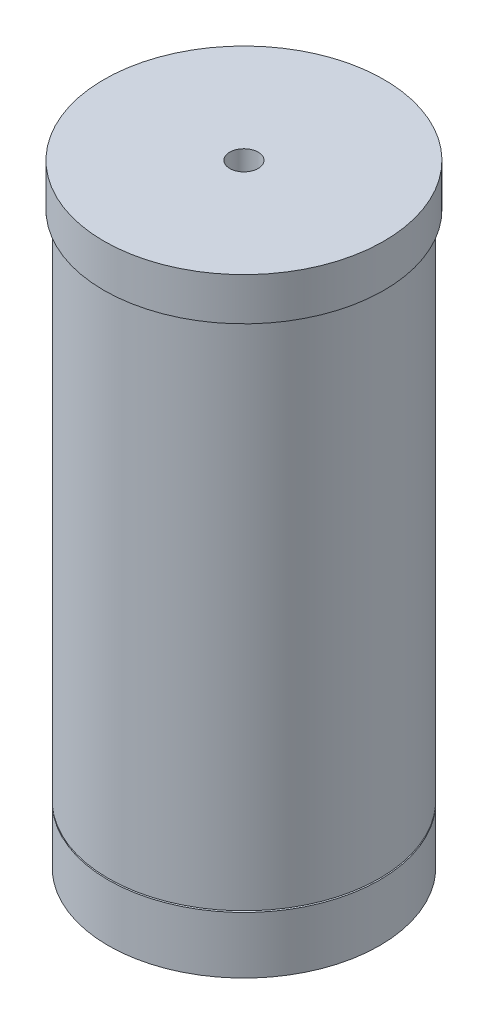
SolidWorks part; units mm, degrees
other "Body"
ref_plane "Front Plane" through (0, 0, 0) normal (0, 0, 1) x (1, 0, 0)
ref_plane "Top Plane" through (0, 0, 0) normal (0, 1, 0) x (1, 0, 0)
ref_plane "Right Plane" through (0, 0, 0) normal (1, 0, 0) x (0, 0, -1)
sketch "Sketch1" plane through (0, 0, 0) normal (0, 1, 0) x (1, 0, 0)
  circle A0 centre (0, 0) radius 47.75
  circle A1 centre (0, 0) radius 5
  circle A2 centre (0, 33) radius 6
  circle A3 centre (23.3345, 23.3345) radius 6
  circle A4 centre (33, 0) radius 6
  circle A5 centre (23.3345, -23.3345) radius 6
  circle A6 centre (0, -33) radius 6
  circle A7 centre (-23.3345, -23.3345) radius 6
  circle A8 centre (-33, 0) radius 6
  circle A9 centre (-23.3345, 23.3345) radius 6
  circle A10 centre (-23.3345, 23.3345) radius 10
  circle A11 centre (-23.3345, 23.3345) radius 11.5
  circle A12 centre (-23.3345, 23.3345) radius 8.5
  circle A13 centre (0, 33) radius 8.5
  circle A14 centre (0, 33) radius 11.5
  circle A15 centre (23.3345, 23.3345) radius 8.5
  circle A16 centre (23.3345, 23.3345) radius 11.5
  circle A17 centre (33, 0) radius 8.5
  circle A18 centre (33, 0) radius 11.5
  circle A19 centre (23.3345, -23.3345) radius 8.5
  circle A20 centre (23.3345, -23.3345) radius 11.5
  circle A21 centre (0, -33) radius 8.5
  circle A22 centre (0, -33) radius 11.5
  circle A23 centre (-23.3345, -23.3345) radius 8.5
  circle A24 centre (-23.3345, -23.3345) radius 11.5
  circle A25 centre (-33, 0) radius 8.5
  circle A26 centre (-33, 0) radius 11.5
  point P22 (0, 0)
  point P56 (0, 0)
  dimension "D1" = 95.5
  dimension "D2" = 10
  dimension "D3" = 33
  dimension "D5" = 20
  dimension "D6" = 1.5
  dimension "D7" = 1.5
  dimension "D4" = 8
  dimension "D8" = 8
extrude "Boss-Extrude1" add sketch "Sketch1" along normal blind 45 contours A0 A26 A24 A22 A20 A18 A16 A14 A11 A1 | A22 A21 | A21 A6 | A24 A23 | A23 A7 | A26 A25 | A25 A8 | A20 A19 | A19 A5 | A18 A17 | A17 A4 | A16 A15 | A15 A3 | A14 A13 | A13 A2 | A11 A10 | A10 A12 | A12 A9 region at (-46.3994, 0, 0) region at (-33.0517, 0, -23.3345) region at (-34.5093, 0, -23.3345) region at (-31.5941, 0, -23.3345) region at (-8.2596, 0, -33) region at (-11.1747, 0, -33) region at (15.0749, 0, -23.3345) region at (12.1598, 0, -23.3345) region at (24.7404, 0, 0) region at (21.8253, 0, 0) region at (15.0749, 0, 23.3345) region at (12.1598, 0, 23.3345) region at (-8.2596, 0, 33) region at (-11.1747, 0, 33) region at (-31.5941, 0, 23.3345) region at (-34.5093, 0, 23.3345) region at (-41.2596, 0, 0) region at (-44.1747, 0, 0)
extrude "Cut-Extrude1" cut sketch "Sketch1<3>" along normal blind 5 contours A24 A23 | A22 A21 | A20 A19 | A18 A17 | A16 A15 | A14 A13 | A10 A12 | A11 A10 | A26 A25 region at (-33.0517, 0, -23.3345) region at (-34.5093, 0, -23.3345) region at (-11.1747, 0, -33) region at (12.1598, 0, -23.3345) region at (21.8253, 0, 0) region at (12.1598, 0, 23.3345) region at (-11.1747, 0, 33) region at (-34.5093, 0, 23.3345) region at (-44.1747, 0, 0)
sketch "Sketch1<3>" plane through (0, 0, 0) normal (0, 1, 0) x (1, 0, 0) same geometry as "Sketch1"
sketch "Sketch3" plane through (0, 45, 0) normal (0, 1, 0) x (1, 0, 0)
  circle A0 centre (0, 0) radius 47.75
  circle A1 centre (0, 0) radius 5
  dimension "D1" = 95.5
extrude "Boss-Extrude2" add sketch "Sketch3" along normal blind 10
sketch "Sketch6" plane through (0, 55, 0) normal (0, 1, 0) x (1, 0, 0)
  line L4 (-10, 34.4976) -> (-10, -34.4976)
  line L6 (-15, 39.4976) -> (-15, -39.4976)
  line L8 (15, 39.4976) -> (15, -39.4976)
  line L10 (10, 34.4976) -> (10, -34.4976)
  line L12 (-9.5, 33.9976) -> (-9.5, -33.9976)
  line L14 (9.5, 33.9976) -> (9.5, -33.9976)
  line L16 (-15, 39.4976) -> (15, 39.4976) construction
  line L17 (-15, -39.4976) -> (15, -39.4976) construction
  line L18 (-10, -34.4976) -> (10, -34.4976) construction
  line L19 (-10, 34.4976) -> (10, 34.4976) construction
  line L20 (-9.5, -33.9976) -> (9.5, -33.9976) construction
  line L21 (-9.5, 33.9976) -> (9.5, 33.9976) construction
  line L22 (-5.5, 30.813) -> (-5.5, -30.813)
  line L23 (5.5, 30.813) -> (5.5, -30.813)
  circle A0 centre (0, 0) radius 49.28
  circle A1 centre (0, 0) radius 42.5
  arc A4 (-15, -39.4976) -> (15, -39.4976) centre (0, 0) ccw
  arc A5 (-10, -34.4976) -> (10, -34.4976) centre (0, 0) ccw
  arc A6 (10, 34.4976) -> (-10, 34.4976) centre (0, 0) ccw
  arc A7 (15, 39.4976) -> (-15, 39.4976) centre (0, 0) ccw
  arc A8 (-9.5, -33.9976) -> (9.5, -33.9976) centre (0, 0) ccw
  arc A9 (9.5, 33.9976) -> (-9.5, 33.9976) centre (0, 0) ccw
  arc A10 (-5.5, -30.813) -> (5.5, -30.813) centre (0, 0) ccw
  arc A11 (5.5, 30.813) -> (-5.5, 30.813) centre (0, 0) ccw
  circle M8 centre (0, 0) radius 47.75
  dimension "D1" = 85
  dimension "D2" = 84.5
  dimension "D4" = 30
  dimension "D6" = 4
  dimension "D3" = 5
  dimension "D5" = 0.5
extrude "Boss-Extrude6" add sketch "Sketch6" along normal blind 125 contours L8 A7 L6 A4 A6 L10 A5 L4 | A1 M8 region at (0, 55, -41.3533) region at (-46.3994, 55, 0)
extrude "Boss-Extrude7" add sketch "Sketch6<4>" along normal blind 20 contours L14 A9 L12 A8 A11 L23 A10 L22 region at (0, 55, -34.5689)
sketch "Sketch6<4>" plane through (0, 55, 0) normal (0, 1, 0) x (1, 0, 0) same geometry as "Sketch6"
ref_plane "Plane1" through (0, -0.5, 0) normal (0, 1, 0) x (1, 0, 0)
sketch "Sketch7" plane through (0, -0.5, 0) normal (0, 1, 0) x (1, 0, 0)
  circle A20 centre (0, 0) radius 47.75
  circle A25 centre (0, 33) radius 8.75
  circle A26 centre (0, 33) radius 11.25
  circle A27 centre (23.3345, 23.3345) radius 11.25
  circle A28 centre (23.3345, 23.3345) radius 8.75
  circle A29 centre (33, 0) radius 11.25
  circle A30 centre (33, 0) radius 8.75
  circle A31 centre (23.3345, -23.3345) radius 11.25
  circle A32 centre (23.3345, -23.3345) radius 8.75
  circle A33 centre (0, -33) radius 11.25
  circle A34 centre (0, -33) radius 8.75
  circle A35 centre (-23.3345, -23.3345) radius 11.25
  circle A36 centre (-23.3345, -23.3345) radius 8.75
  circle A37 centre (-33, 0) radius 11.25
  circle A38 centre (-33, 0) radius 8.75
  circle A39 centre (-23.3345, 23.3345) radius 11.25
  circle A40 centre (-23.3345, 23.3345) radius 8.75
  point P30 (0, 0)
  point P31 (2.4142, -3.0231)
  dimension "D1" = 8
extrude "Boss-Extrude8" add sketch "Sketch7" along normal blind 2 separate body contours A31 A32 | A29 A30 | A27 A28 | A26 A25 | A39 A40 | A37 A38 | A35 A36 | A33 A34 region at (-10.9318, -0.5, -33) region at (12.4027, -0.5, -23.3345) region at (22.0682, -0.5, 0) region at (12.4027, -0.5, 23.3345) region at (-10.9318, -0.5, 33) region at (-34.2663, -0.5, 23.3345) region at (-43.9318, -0.5, 0) region at (-34.2663, -0.5, -23.3345)
extrude "Boss-Extrude9" add sketch "Sketch7<4>" against normal blind 20 contours A26 | A27 | A27 | A25 | A29 | A29 | A35 | A35 | A37 | A37 | A39 | A39 | A26 A25 | A30 | A28 | A40 | A38 | A36 | A34 | A32 | A31 A32 | A33 A34 region at (0, -0.5, 0) region at (0, -0.5, -33) region at (-10.9318, -0.5, -33) region at (12.4027, -0.5, -23.3345) region at (23.3345, -0.5, -23.3345) region at (22.0682, -0.5, 0) region at (33, -0.5, 0) region at (12.4027, -0.5, 23.3345) region at (23.3345, -0.5, 23.3345) region at (-10.9318, -0.5, 33) region at (0, -0.5, 33) region at (-34.2663, -0.5, 23.3345) region at (-23.3345, -0.5, 23.3345) region at (-43.9318, -0.5, 0) region at (-33, -0.5, 0) region at (-34.2663, -0.5, -23.3345) region at (-23.3345, -0.5, -23.3345)
sketch "Sketch7<4>" plane through (0, -0.5, 0) normal (0, 1, 0) x (1, 0, 0) same geometry as "Sketch7"
sketch "Sketch8" plane through (0, 180, 0) normal (0, 1, 0) x (1, 0, 0)
  line L2 (-9.5, 33.9976) -> (-9.5, -33.9976)
  line L4 (9.5, 33.9976) -> (9.5, -33.9976)
  circle A0 centre (0, 0) radius 49.28
  arc A1 (-9.5, -33.9976) -> (9.5, -33.9976) centre (0, 0) ccw
  arc A2 (9.5, 33.9976) -> (-9.5, 33.9976) centre (0, 0) ccw
  circle A3 centre (0, 0) radius 5
  circle M7 centre (0, 0) radius 42.5
  circle M8 centre (0, 0) radius 47.75
extrude "Boss-Extrude10" add sketch "Sketch8" along normal blind 15 separate body contours A2 L4 A1 L2 M7 | M8 M7 | L4 A2 L2 A1 A3 | A0 M8 region at (0, 180, -34.5689) region at (-47.8862, 180, 0) region at (-41.2979, 180, 0) region at (-46.3994, 180, 0)
extrude "Boss-Extrude11" add sketch "Sketch8<4>" against normal blind 25 contours L4 A2 L2 A1 A3 region at (0, 180, -34.5689)
sketch "Sketch8<4>" plane through (0, 180, 0) normal (0, 1, 0) x (1, 0, 0) same geometry as "Sketch8"
